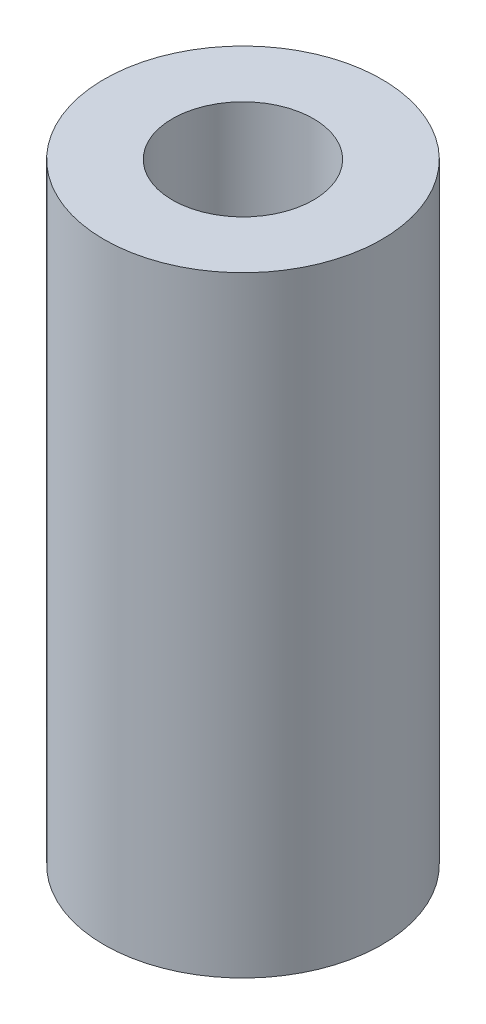
SolidWorks part; units mm, degrees
ref_plane "Front Plane" through (0, 0, 0) normal (0, 0, 1) x (1, 0, 0)
ref_plane "Top Plane" through (0, 0, 0) normal (0, 1, 0) x (1, 0, 0)
ref_plane "Right Plane" through (0, 0, 0) normal (1, 0, 0) x (0, 0, -1)
sketch "Sketch1" plane through (0, 0, 0) normal (0, 1, 0) x (1, 0, 0)
  circle A0 centre (0, 0) radius 6.35
  arc A4 (5.4055, 3.3322) -> (-6.2785, -0.9501) centre (0, 0) ccw construction
  circle A5 centre (0, 0) radius 3.2258
  circle A6 centre (0, 0) radius 3.2258
  dimension "D1" = 0.0508
extrude "Boss-Extrude1" add sketch "Sketch1" along normal up to surface (27.9373 mm away)
